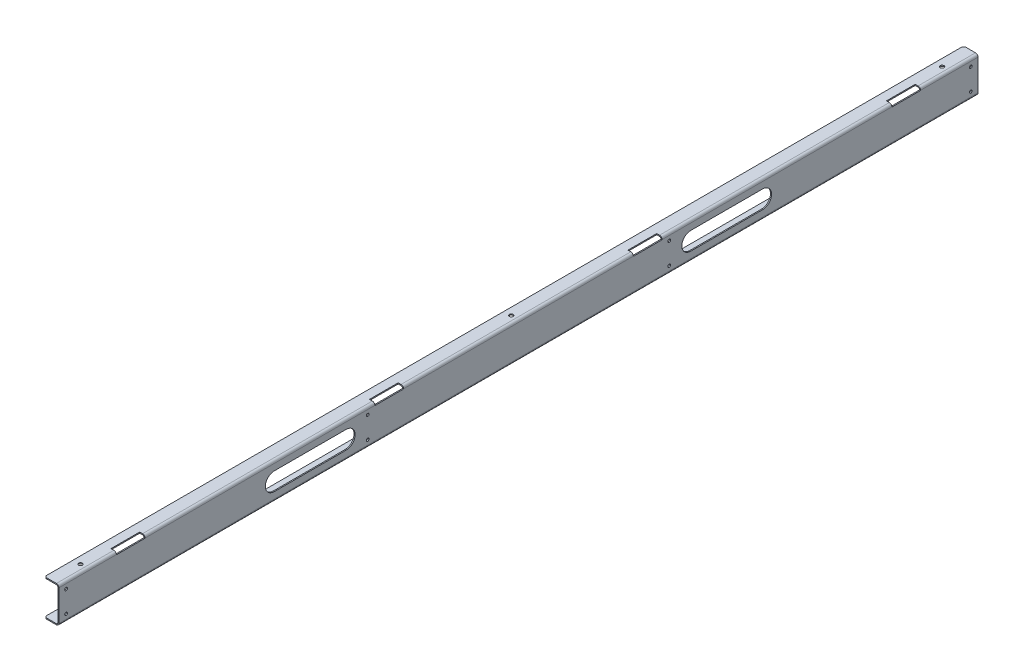
SolidWorks part; units mm, degrees
note: The reader was unsure of these and kept them because the rebuilt part matched: flange length of "Edge-Flange1".
material "Plain Carbon Steel"
ref_plane "Front Plane" through (0, 0, 0) normal (0, 0, 1) x (1, 0, 0)
ref_plane "Top Plane" through (0, 0, 0) normal (0, 1, 0) x (1, 0, 0)
ref_plane "Right Plane" through (0, 0, 0) normal (1, 0, 0) x (0, 0, -1)
sketch "Sketch1" plane through (0, 0, 0) normal (1, 0, 0) x (0, 0, -1)
  line L1 (0, 0) -> (1625.6, 0)
  line L2 (0, 0) -> (0, 63.5)
  line L3 (0, 63.5) -> (1625.6, 63.5)
  line L4 (1625.6, 0) -> (1625.6, 63.5)
  dimension "D1" = 1625.6
  dimension "D2" = 63.5
base flange "Base-Flange1" sketch "Sketch1" thickness 1.8974 reverse thickness direction no parameters "D1"=2.54
edge flange "Edge-Flange1" sketch "Sketch10" flange profiles "Sketch10", "Sketch11" flange angle 90 flange length 25.4 flange position material inside bend radius 2.54 thickness 1.8974 relief rectangular parameters "D6"=10, "D8"=0.254
sketch "Sketch10" plane through (-1.8974, 63.5, 0) normal (0, -1, 0) x (0, 0, 1)
  line L2 (-1625.6, 0) -> (-1625.6, 23.5026)
  line L3 (-1625.6, 23.5026) -> (0, 23.5026)
  line L4 (0, 23.5026) -> (0, 0)
  line L5 (0, 0) -> (-1625.6, 0) construction
  line L6 (0, 0) -> (-1625.6, 0)
sketch "Sketch11" plane through (-1.8974, 0, 0) normal (0, 1, 0) x (0, 0, -1)
  line L0 (1625.6, 0) -> (0, 0) construction
  line L1 (1625.6, 0) -> (0, 0)
  line L2 (1625.6, 0) -> (1625.6, 23.5026)
  line L3 (1625.6, 23.5026) -> (0, 23.5026)
  line L4 (0, 23.5026) -> (0, 0)
bend "EdgeBend1" bend radius 2.54 bend angle 90 parameters "D5"=1
bend "EdgeBend2" bend radius 2.54 bend angle 90 parameters "D5"=2
sketch "Sketch15" plane through (0, 63.5, 0) normal (0, 1, 0) x (1, 0, 0)
  line L0 (0, 1625.6) -> (0, 0) construction
  line L1 (0, 101.6) -> (-9.525, 101.6)
  line L2 (0, 101.6) -> (0, 152.4)
  line L3 (0, 152.4) -> (-9.525, 152.4)
  line L4 (-9.525, 101.6) -> (-9.525, 152.4)
  point P6 (0, 812.8)
  dimension "D1" = 50.8
  dimension "D2" = 711.2
  dimension "D3" = 9.525
extrude "Cut-Extrude2" cut sketch "Sketch15" against normal blind 4.7752 normal cut yes
pattern_linear "LPattern3" count 4 spacing 457.2 along (0, 0, -1) of "Cut-Extrude2"
sketch "Sketch16" plane through (0, 63.5, 0) normal (0, 1, 0) x (1, 0, 0)
  line L0 (-25.4, 0) -> (-25.4, 1625.6) construction
  line L1 (0, 1625.6) -> (0, 1524) construction
  circle A0 centre (-12.7, 1574.8) radius 3.3655
  point P4 (-25.4, 812.8)
  dimension "D1" = 6.731
  dimension "D2" = 12.7
  dimension "D3" = 762
extrude "Cut-Extrude3" cut sketch "Sketch16" against normal blind 2.54
pattern_linear "LPattern4" count 3 spacing 762 along (0, 0, 1) of "Cut-Extrude3"
sketch "Sketch17" plane through (0, 0, 0) normal (1, 0, 0) x (0, 0, -1)
  line L0 (381, 31.75) -> (508, 31.75) construction
  line L1 (381, 47.625) -> (508, 47.625)
  line L2 (381, 15.875) -> (508, 15.875)
  line L4 (609.6, 63.5) -> (1016, 63.5) construction
  line L5 (152.4, 63.5) -> (558.8, 63.5) construction
  arc A0 (381, 47.625) -> (381, 15.875) centre (381, 31.75) ccw
  arc A1 (508, 15.875) -> (508, 47.625) centre (508, 31.75) ccw
  point P2 (444.5, 31.75)
  point P12 (812.8, 63.5)
  dimension "D1" = 127
  dimension "D2" = 31.75
  dimension "D3" = 304.8
  dimension "D4" = 31.75
extrude "Cut-Extrude4" cut sketch "Sketch17" against normal blind 2.54 normal cut yes
pattern_linear "LPattern5" count 2 spacing 736.6 along (0, 0, -1) of "Cut-Extrude4"
ref_plane "Plane1" through (0, 0, -812.8) normal (0, 0, 1) x (1, 0, 0)
sketch "Sketch18" plane through (0, 0, 0) normal (1, 0, 0) x (0, 0, -1)
  line L0 (609.6, 63.5) -> (1016, 63.5) construction
  circle A0 centre (546.1, 50.8) radius 2.4638
  circle A1 centre (546.1, 12.7) radius 2.4638
  point P7 (812.8, 63.5)
  dimension "D1" = 4.9276
  dimension "D2" = 12.7
  dimension "D3" = 38.1
  dimension "D4" = 266.7
extrude "Cut-Extrude5" cut sketch "Sketch18" against normal through all normal cut yes
sketch "Sketch19" plane through (0, 0, 0) normal (1, 0, 0) x (0, 0, -1)
  line L0 (0, 59.0626) -> (0, 4.4374) construction
  line L1 (0, 63.5) -> (101.6, 63.5) construction
  circle A0 centre (12.7, 50.8) radius 2.4638
  circle A1 centre (12.7, 12.7) radius 2.4638
  dimension "D1" = 12.7
  dimension "D4" = 4.9276
  dimension "D2" = 12.7
  dimension "D3" = 38.1
extrude "Cut-Extrude6" cut sketch "Sketch19" against normal through all normal cut yes
mirror "Mirror1" about plane through (0, 0, -812.8) normal (0, 0, 1) of "Cut-Extrude6", "Cut-Extrude5"
chamfer "Chamfer1" distance 2.54 angle 45 4 edges at (-25.4, 0.9487, -1625.6) (-25.4, 62.5513, -1625.6) (-25.4, 0.9487, 0) (-25.4, 62.5513, 0)
sketch "Bend-Lines1" [suppressed] plane through (0, 0, 0) normal (0, 1, 0) x (1, 0, 0)
sketch "Bounding-Box1" [suppressed] plane through (0, 0, 0) normal (0, 1, 0) x (1, 0, 0)
sheet metal parameters "Sheet-Metal1" thickness 1.8974 parameters "D1"=2.54
flat pattern "Flat-Pattern1" [suppressed]
sketch "Bend-Lines2" plane through (0, 0, 0) normal (0, 1, 0) x (1, 0, 0)
sketch3d "Bounding-Box2" [suppressed]
  line L0 (1625.6, 0, 0) -> (0, 0, 0) construction
  line L1 (1625.6, 63.5, 0) -> (0, 63.5, 0) construction
  line L2 (1625.6, 0, 0) -> (1625.6, 63.5, 0) construction
  line L3 (0, 0, 0) -> (0, 63.5, 0) construction
sheet metal parameters "Sheet-Metal2" thickness 1.8974 parameters "D1"=2.54
flat pattern "Flat-Pattern1"
sketch "Bend-Lines2" plane through (0, 0, 0) normal (1, 0, 0) x (0, 0, -1)
  line L0 (0, 1.6974) -> (1625.6, 1.6974) construction
  line L1 (1625.6, 61.8026) -> (0, 61.8026) construction
  line L2 (0, 1.6974) -> (1625.6, 1.6974) construction
  line L3 (1625.6, 61.8026) -> (0, 61.8026) construction
sketch3d "Bounding-Box2" [suppressed]
  line L0 (1625.6, -22.0053, 0) -> (0, -22.0053, 0) construction
  line L1 (1625.6, 85.5053, 0) -> (0, 85.5053, 0) construction
  line L2 (1625.6, -22.0053, 0) -> (1625.6, 85.5053, 0) construction
  line L3 (0, -22.0053, 0) -> (0, 85.5053, 0) construction
bend of the flat pattern "Flatten-<EdgeBend1>1"
bend of the flat pattern "Flatten-<EdgeBend2>1"
sheet metal parameters "Sheet-Metal6" thickness 1.8974 parameters "D1"=2.54
flat pattern "Flat-Pattern1"
sketch "Bend-Lines2" plane through (0, 0, 0) normal (1, 0, 0) x (0, 0, -1)
  line L0 (0, 1.6974) -> (1616.71, 1.6974) construction
  line L1 (97.155, 55.4526) -> (0, 55.4526) construction
  line L2 (0, 1.6974) -> (1616.71, 1.6974) construction
  line L3 (97.155, 55.4526) -> (0, 55.4526) construction
  line L4 (1616.71, 55.4526) -> (147.955, 55.4526) construction
sketch3d "Bounding-Box2" [suppressed]
  line L0 (1619.25, -22.0053, 0) -> (-2.54, -22.0053, 0) construction
  line L1 (1619.25, 79.1553, 0) -> (-2.54, 79.1553, 0) construction
  line L2 (1619.25, -22.0053, 0) -> (1619.25, 79.1553, 0) construction
  line L3 (-2.54, -22.0053, 0) -> (-2.54, 79.1553, 0) construction
bend of the flat pattern "Flatten-<EdgeBend1>1"
bend of the flat pattern "Flatten-<EdgeBend2>1"
sheet metal parameters "Sheet-Metal7" thickness 1.8974 parameters "D1"=2.54
flat pattern "Flat-Pattern1" [suppressed]
sketch "Bend-Lines2" plane through (0, 0, 0) normal (1, 0, 0) x (0, 0, -1)
  line L0 (0, 1.6974) -> (1625.6, 1.6974) construction
  line L1 (558.8, 61.8026) -> (152.4, 61.8026) construction
  line L2 (0, 1.6974) -> (1625.6, 1.6974) construction
  line L3 (558.8, 61.8026) -> (152.4, 61.8026) construction
  line L4 (101.6, 61.8026) -> (0, 61.8026) construction
  line L5 (1625.6, 61.8026) -> (1524, 61.8026) construction
  line L6 (1473.2, 61.8026) -> (1066.8, 61.8026) construction
  line L7 (1016, 61.8026) -> (609.6, 61.8026) construction
sketch3d "Bounding-Box2" [suppressed]
  line L0 (1628.14, -22.0053, 0) -> (0, -22.0053, 0) construction
  line L1 (1628.14, 85.5053, 0) -> (0, 85.5053, 0) construction
  line L2 (1628.14, -22.0053, 0) -> (1628.14, 85.5053, 0) construction
  line L3 (0, -22.0053, 0) -> (0, 85.5053, 0) construction
bend of the flat pattern "Flatten-<EdgeBend1>1"
bend of the flat pattern "Flatten-<EdgeBend2>1"
sketch "Sketch16-1" [suppressed] plane through (0, 60.1053, 0) normal (1, 0, 0) x (0, -1, 0)
  line L0 (-25.4, 0) -> (-25.4, 1625.6) construction
  circle A0 centre (-12.7, 1574.8) radius 3.3655
  dimension "D1" = 6.731
  dimension "D2" = 12.7
sheet metal parameters "Sheet-Metal8" thickness 1.8974 parameters "D1"=2.54
flat pattern "Flat-Pattern1"
sketch "Bend-Lines2" plane through (0, 0, 0) normal (1, 0, 0) x (0, 0, -1)
  line L0 (0, 1.6974) -> (1616.71, 1.6974) construction
  line L1 (554.355, 55.4526) -> (147.955, 55.4526) construction
  line L2 (0, 1.6974) -> (1616.71, 1.6974) construction
  line L3 (554.355, 55.4526) -> (147.955, 55.4526) construction
  line L4 (97.155, 55.4526) -> (0, 55.4526) construction
  line L5 (1616.71, 55.4526) -> (1519.555, 55.4526) construction
  line L6 (1468.755, 55.4526) -> (1062.355, 55.4526) construction
  line L7 (1011.555, 55.4526) -> (605.155, 55.4526) construction
sketch3d "Bounding-Box2" [suppressed]
  line L0 (1619.25, -22.0053, 0) -> (-2.54, -22.0053, 0) construction
  line L1 (1619.25, 79.1553, 0) -> (-2.54, 79.1553, 0) construction
  line L2 (1619.25, -22.0053, 0) -> (1619.25, 79.1553, 0) construction
  line L3 (-2.54, -22.0053, 0) -> (-2.54, 79.1553, 0) construction
bend of the flat pattern "Flatten-<EdgeBend1>1"
bend of the flat pattern "Flatten-<EdgeBend2>1"
sheet metal parameters "Sheet-Metal9" thickness 1.8974 parameters "D1"=2.54
flat pattern "Flat-Pattern1"
sketch "Bend-Lines2" plane through (0, 0, 0) normal (1, 0, 0) x (0, 0, -1)
  line L0 (0, 1.6974) -> (1616.71, 1.6974) construction
  line L1 (554.355, 61.8026) -> (147.955, 61.8026) construction
  line L2 (0, 1.6974) -> (1616.71, 1.6974) construction
  line L3 (554.355, 61.8026) -> (147.955, 61.8026) construction
  line L4 (97.155, 61.8026) -> (0, 61.8026) construction
  line L5 (1616.71, 61.8026) -> (1519.555, 61.8026) construction
  line L6 (1468.755, 61.8026) -> (1062.355, 61.8026) construction
  line L7 (1011.555, 61.8026) -> (605.155, 61.8026) construction
sketch3d "Bounding-Box2" [suppressed]
  line L0 (1619.25, -22.0053, 0) -> (-2.54, -22.0053, 0) construction
  line L1 (1619.25, 85.5053, 0) -> (-2.54, 85.5053, 0) construction
  line L2 (1619.25, -22.0053, 0) -> (1619.25, 85.5053, 0) construction
  line L3 (-2.54, -22.0053, 0) -> (-2.54, 85.5053, 0) construction
bend of the flat pattern "Flatten-<EdgeBend1>1"
bend of the flat pattern "Flatten-<EdgeBend2>1"
sheet metal parameters "Sheet-Metal10" thickness 1.8974 parameters "D1"=2.54
flat pattern "Flat-Pattern1"
sketch "Bend-Lines2" plane through (0, 0, 0) normal (1, 0, 0) x (0, 0, -1)
  line L0 (0, 1.6974) -> (1616.71, 1.6974) construction
  line L1 (554.355, 61.8026) -> (147.955, 61.8026) construction
  line L2 (0, 1.6974) -> (1616.71, 1.6974) construction
  line L3 (554.355, 61.8026) -> (147.955, 61.8026) construction
  line L4 (97.155, 61.8026) -> (0, 61.8026) construction
  line L5 (1616.71, 61.8026) -> (1519.555, 61.8026) construction
  line L6 (1468.755, 61.8026) -> (1062.355, 61.8026) construction
  line L7 (1011.555, 61.8026) -> (605.155, 61.8026) construction
sketch3d "Bounding-Box2" [suppressed]
  line L0 (1619.25, -22.0053, 0) -> (-2.54, -22.0053, 0) construction
  line L1 (1619.25, 85.5053, 0) -> (-2.54, 85.5053, 0) construction
  line L2 (1619.25, -22.0053, 0) -> (1619.25, 85.5053, 0) construction
  line L3 (-2.54, -22.0053, 0) -> (-2.54, 85.5053, 0) construction
bend of the flat pattern "Flatten-<EdgeBend1>1"
bend of the flat pattern "Flatten-<EdgeBend2>1"
sheet metal parameters "Sheet-Metal11" thickness 1.8974 parameters "D1"=2.54
flat pattern "Flat-Pattern1"
sketch "Bend-Lines2" plane through (0, 0, 0) normal (1, 0, 0) x (0, 0, -1)
  line L0 (0, 1.6974) -> (1625.6, 1.6974) construction
  line L1 (558.8, 61.8026) -> (152.4, 61.8026) construction
  line L2 (0, 1.6974) -> (1625.6, 1.6974) construction
  line L3 (558.8, 61.8026) -> (152.4, 61.8026) construction
  line L4 (101.6, 61.8026) -> (0, 61.8026) construction
  line L5 (1625.6, 61.8026) -> (1524, 61.8026) construction
  line L6 (1473.2, 61.8026) -> (1066.8, 61.8026) construction
  line L7 (1016, 61.8026) -> (609.6, 61.8026) construction
sketch3d "Bounding-Box2" [suppressed]
  line L0 (1625.6, -22.0053, 0) -> (0, -22.0053, 0) construction
  line L1 (1625.6, 85.5053, 0) -> (0, 85.5053, 0) construction
  line L2 (1625.6, -22.0053, 0) -> (1625.6, 85.5053, 0) construction
  line L3 (0, -22.0053, 0) -> (0, 85.5053, 0) construction
bend of the flat pattern "Flatten-<EdgeBend1>1"
bend of the flat pattern "Flatten-<EdgeBend2>1"
sheet metal parameters "Sheet-Metal12" thickness 1.8974 parameters "D1"=2.54
flat pattern "Flat-Pattern1"
sketch "Bend-Lines2" plane through (0, 0, 0) normal (1, 0, 0) x (0, 0, -1)
  line L0 (0, 1.6974) -> (1625.6, 1.6974) construction
  line L1 (558.8, 61.8026) -> (152.4, 61.8026) construction
  line L2 (0, 1.6974) -> (1625.6, 1.6974) construction
  line L3 (558.8, 61.8026) -> (152.4, 61.8026) construction
  line L4 (101.6, 61.8026) -> (0, 61.8026) construction
  line L5 (1625.6, 61.8026) -> (1524, 61.8026) construction
  line L6 (1473.2, 61.8026) -> (1066.8, 61.8026) construction
  line L7 (1016, 61.8026) -> (609.6, 61.8026) construction
sketch3d "Bounding-Box2" [suppressed]
  line L0 (1625.6, -22.0053, 0) -> (0, -22.0053, 0) construction
  line L1 (1625.6, 85.5053, 0) -> (0, 85.5053, 0) construction
  line L2 (1625.6, -22.0053, 0) -> (1625.6, 85.5053, 0) construction
  line L3 (0, -22.0053, 0) -> (0, 85.5053, 0) construction
bend of the flat pattern "Flatten-<EdgeBend1>1"
bend of the flat pattern "Flatten-<EdgeBend2>1"
sheet metal parameters "Sheet-Metal13" thickness 1.8974 parameters "D1"=2.54
flat pattern "Flat-Pattern1"
sketch "Bend-Lines2" plane through (0, 0, 0) normal (1, 0, 0) x (0, 0, -1)
  line L0 (0, 1.6974) -> (1625.6, 1.6974) construction
  line L1 (558.8, 61.8026) -> (152.4, 61.8026) construction
  line L2 (0, 1.6974) -> (1625.6, 1.6974) construction
  line L3 (558.8, 61.8026) -> (152.4, 61.8026) construction
  line L4 (101.6, 61.8026) -> (0, 61.8026) construction
  line L5 (1625.6, 61.8026) -> (1524, 61.8026) construction
  line L6 (1473.2, 61.8026) -> (1066.8, 61.8026) construction
  line L7 (1016, 61.8026) -> (609.6, 61.8026) construction
sketch3d "Bounding-Box2" [suppressed]
  line L0 (1625.6, -22.0053, 0) -> (0, -22.0053, 0) construction
  line L1 (1625.6, 85.5053, 0) -> (0, 85.5053, 0) construction
  line L2 (1625.6, -22.0053, 0) -> (1625.6, 85.5053, 0) construction
  line L3 (0, -22.0053, 0) -> (0, 85.5053, 0) construction
bend of the flat pattern "Flatten-<EdgeBend1>1"
bend of the flat pattern "Flatten-<EdgeBend2>1"
sheet metal parameters "Sheet-Metal14" thickness 1.8974 parameters "D1"=2.54
flat pattern "Flat-Pattern1"
sketch "Bend-Lines2" plane through (0, 0, 0) normal (1, 0, 0) x (0, 0, -1)
  line L0 (0, 1.6974) -> (1625.6, 1.6974) construction
  line L1 (558.8, 61.8026) -> (152.4, 61.8026) construction
  line L2 (0, 1.6974) -> (1625.6, 1.6974) construction
  line L3 (558.8, 61.8026) -> (152.4, 61.8026) construction
  line L4 (101.6, 61.8026) -> (0, 61.8026) construction
  line L5 (1625.6, 61.8026) -> (1524, 61.8026) construction
  line L6 (1473.2, 61.8026) -> (1066.8, 61.8026) construction
  line L7 (1016, 61.8026) -> (609.6, 61.8026) construction
sketch3d "Bounding-Box2" [suppressed]
  line L0 (1625.6, -22.0053, 0) -> (0, -22.0053, 0) construction
  line L1 (1625.6, 85.5053, 0) -> (0, 85.5053, 0) construction
  line L2 (1625.6, -22.0053, 0) -> (1625.6, 85.5053, 0) construction
  line L3 (0, -22.0053, 0) -> (0, 85.5053, 0) construction
bend of the flat pattern "Flatten-<EdgeBend1>1"
bend of the flat pattern "Flatten-<EdgeBend2>1"
